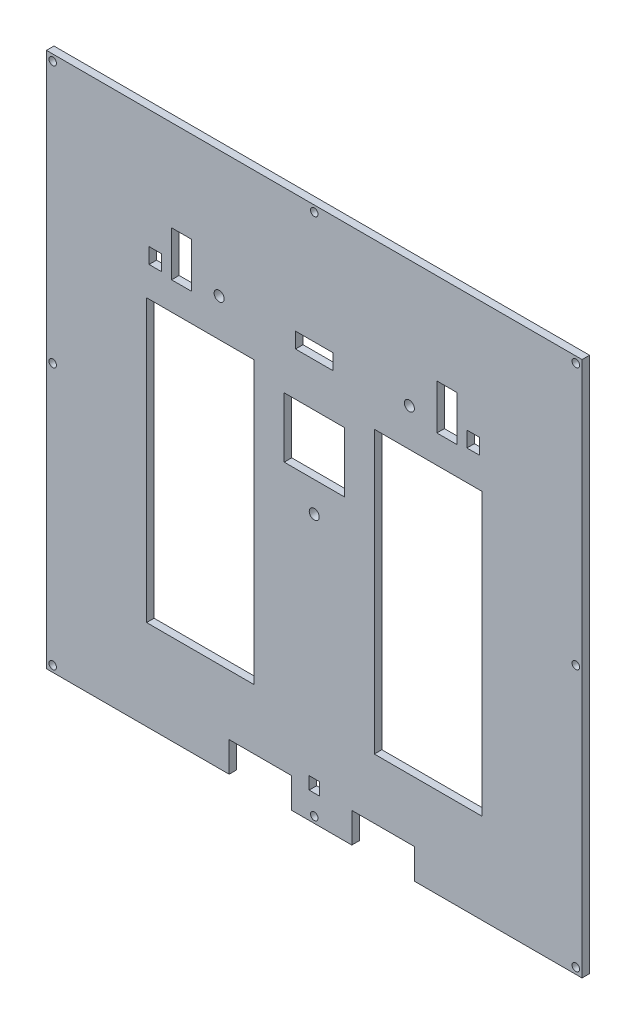
SolidWorks part; units mm, degrees
material "Oak"
ref_plane "Front Plane" through (0, 0, 0) normal (0, 0, 1) x (1, 0, 0)
ref_plane "Top Plane" through (0, 0, 0) normal (0, 1, 0) x (1, 0, 0)
ref_plane "Right Plane" through (0, 0, 0) normal (1, 0, 0) x (0, 0, -1)
sketch "Sketch1" plane through (0, 0, 0) normal (0, 0, 1) x (1, 0, 0)
  line L0 (-61, 53.4) -> (61, 53.4) construction
  line L1 (0, 53.4) -> (0, 0) construction
  line L2 (89, 107) -> (107, 107)
  line L3 (53, 52.6) -> (53, 70.6) construction
  line L4 (57, 52.6) -> (49, 52.6)
  line L5 (57, 52.6) -> (57, 70.6)
  line L6 (0, -91.5) -> (0, -107) construction
  line L7 (-107, -107) -> (107, -107)
  line L8 (-107, 52.4) -> (-107, 107)
  line L9 (-107, 107) -> (-89, 107)
  line L10 (107, 52.4) -> (107, 107)
  line L11 (-107, -107) -> (107, 107) construction
  line L12 (-107, 107) -> (107, -107) construction
  line L13 (-66, 59.6) -> (-61, 59.6)
  line L14 (-66, 59.6) -> (-66, 53.4)
  line L15 (-66, 53.4) -> (-61, 53.4)
  line L16 (-61, 59.6) -> (-61, 53.4)
  line L17 (66, 59.6) -> (61, 59.6)
  line L18 (66, 59.6) -> (66, 53.4)
  line L19 (66, 53.4) -> (61, 53.4)
  line L20 (61, 59.6) -> (61, 53.4)
  line L21 (-2.05, -96.5) -> (2.05, -96.5)
  line L22 (-2.05, -96.5) -> (-2.05, -91.5)
  line L23 (-2.05, -91.5) -> (2.05, -91.5)
  line L24 (2.05, -96.5) -> (2.05, -91.5)
  line L25 (57, 70.6) -> (49, 70.6)
  line L26 (49, 52.6) -> (49, 70.6)
  line L27 (-57, 52.6) -> (-49, 52.6)
  line L28 (-57, 52.6) -> (-57, 70.6)
  line L29 (-57, 70.6) -> (-49, 70.6)
  line L30 (-49, 52.6) -> (-49, 70.6)
  line L31 (-53, 52.6) -> (-53, 70.6) construction
  line L32 (-107, 52.4) -> (-107, -107)
  line L33 (-7.5, 53.4) -> (7.5, 53.4)
  line L34 (-7.5, 53.4) -> (-7.5, 59.6)
  line L35 (-7.5, 59.6) -> (7.5, 59.6)
  line L36 (7.5, 53.4) -> (7.5, 59.6)
  line L37 (-38, 56.5) -> (38, 56.5) construction
  line L38 (0, 53.4) -> (0, 59.6) construction
  line L39 (107, -107) -> (107, 52.4)
  line L40 (-89, 107) -> (89, 107)
  line L41 (67, 41.4) -> (67, -71)
  line L45 (-67, 41.4) -> (-24, 41.4)
  line L49 (-67, 41.4) -> (-67, -71)
  line L50 (-67, -71) -> (-24, -71)
  line L51 (-24, 41.4) -> (-24, -71)
  line L52 (67, 41.4) -> (24, 41.4)
  line L53 (24, 41.4) -> (24, -71)
  line L54 (67, -71) -> (24, -71)
  circle A0 centre (-104.5, 104.5) radius 1.5
  circle A1 centre (104.5, 104.5) radius 1.5
  circle A2 centre (104.5, 0) radius 1.5
  circle A3 centre (-38, 56.5) radius 2
  circle A4 centre (0, 104.5) radius 1.5
  circle A5 centre (104.5, -104.5) radius 1.5
  circle A6 centre (0, 0) radius 2
  circle A7 centre (0, -104.5) radius 1.5
  circle A8 centre (-104.5, -104.5) radius 1.5
  circle A9 centre (-104.5, 0) radius 1.5
  circle A10 centre (38, 56.5) radius 2
  point P0 (0, 0)
  point P1 (0, 0)
  point P66 (0, 0)
  point P69 (0, 56.5)
  dimension "D4" = 3
  dimension "D16" = 4
  dimension "D23" = 38
  dimension "D2" = 122
  dimension "D3" = 214
  dimension "D5" = 209
  dimension "D6" = 6.2
  dimension "D7" = 5
  dimension "D8" = 47.4
  dimension "D9" = 198.5
  dimension "D10" = 18
  dimension "D11" = 53
  dimension "D12" = 1
  dimension "D13" = 4
  dimension "D14" = 40
  dimension "D15" = 214
  dimension "D17" = 53
  dimension "D18" = 8
  dimension "D19" = 7
  dimension "D20" = 18
  dimension "D21" = 15
  dimension "D22" = 4.1
  dimension "D27" = 12
  dimension "D28" = 24
  dimension "D29" = 36
extrude "Boss-Extrude1" add sketch "Sketch1" along normal blind 3
sketch "Sketch3" plane through (0, 0, 3) normal (0, 0, 1) x (1, 0, 0)
  line L0 (-107, -107) -> (107, -107) construction
  line L1 (-34, -107) -> (-9, -107)
  line L2 (-34, -107) -> (-34, -95)
  line L3 (-34, -95) -> (-9, -95)
  line L4 (-9, -107) -> (-9, -95)
  line L6 (15, -107) -> (40, -107)
  line L7 (15, -107) -> (15, -95)
  line L8 (15, -95) -> (40, -95)
  line L9 (40, -107) -> (40, -95)
  line L10 (-12, 12) -> (12, 12)
  line L11 (-12, 12) -> (-12, 36)
  line L12 (-12, 36) -> (12, 36)
  line L13 (12, 12) -> (12, 36)
  line L14 (-12, 12) -> (12, 36) construction
  line L15 (-12, 36) -> (12, 12) construction
  circle A0 centre (0, -104.5) radius 1.5 construction
  point P10 (0, 24)
  dimension "D1" = 12
  dimension "D2" = 15
  dimension "D3" = 40
  dimension "D4" = 9
  dimension "D5" = 34
  dimension "D6" = 24
  dimension "D7" = 24
  dimension "D8" = 12
extrude "Cut-Extrude2" cut sketch "Sketch3" against normal through all
equation "\"bed-plate-thickness\"=3"
equation "\"D1@Boss-Extrude1\"=\"bed-plate-thickness\""
equation "\"D22@Sketch1\"=\"y-cross-rib-thickness\"+0.1"
equation "\"D6@Sketch1\"=\"y-rib-thickness\"+0.2"
equation "\"y-cross-rib-thickness\"=4"
equation "\"y-rib-thickness\"=6"
equation "\"x-plate-thickness\"=5"
equation "\"rod-diameter\"=12"
equation "\"t-nut-hole-diameter\"=3"
